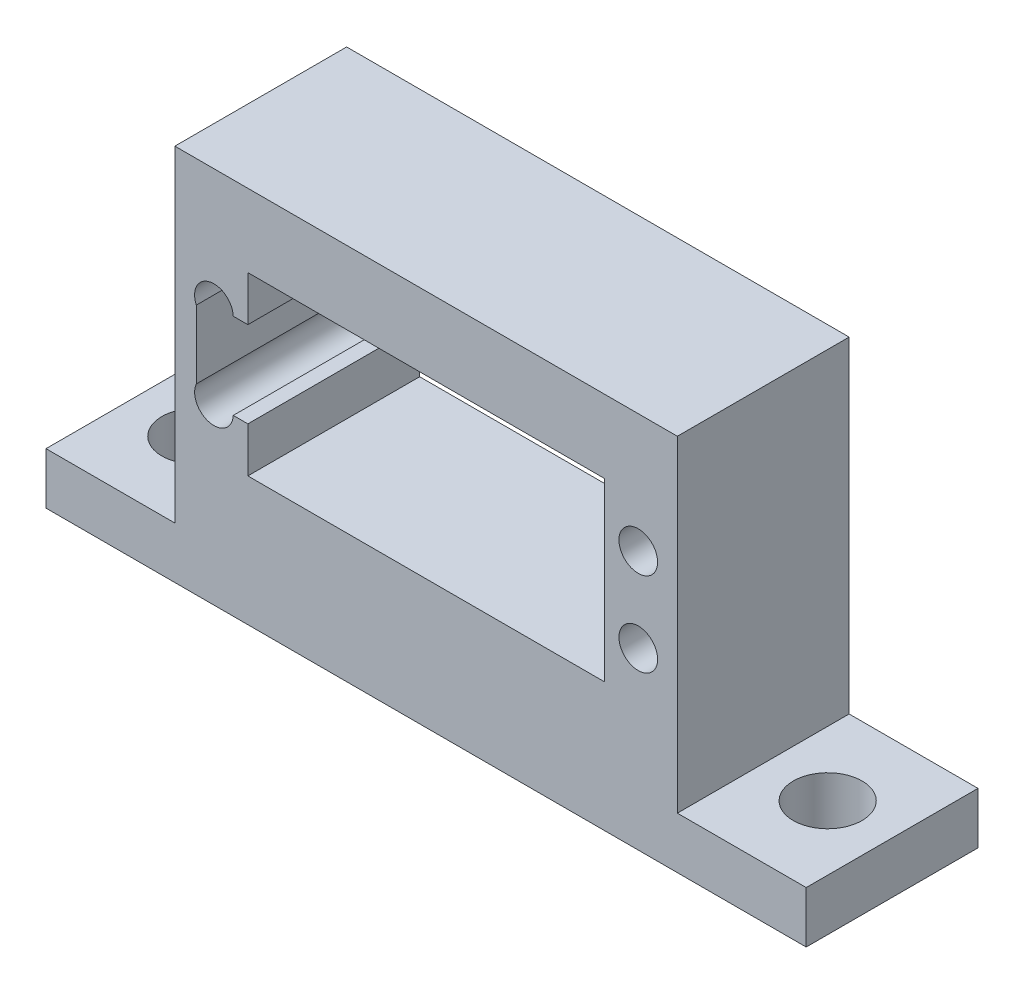
SolidWorks part; units mm, degrees
ref_plane "Front Plane" through (0, 0, 0) normal (0, 0, 1) x (1, 0, 0)
ref_plane "Top Plane" through (0, 0, 0) normal (0, 1, 0) x (1, 0, 0)
ref_plane "Right Plane" through (0, 0, 0) normal (1, 0, 0) x (0, 0, -1)
sketch "Sketch1" plane through (0, 0, 0) normal (0, 0, 1) x (1, 0, 0)
  line L0 (-44.25, 0) -> (44.25, 0)
  line L1 (44.25, 0) -> (44.25, 6)
  line L2 (44.25, 6) -> (29.25, 6)
  line L3 (29.25, 6) -> (29.25, 44)
  line L4 (29.25, 44) -> (-29.25, 44)
  line L5 (0, 0) -> (0, 132.122) construction
  line L6 (-20.75, 35.5) -> (20.75, 35.5)
  line L7 (20.75, 35.5) -> (20.75, 15)
  line L8 (20.75, 15) -> (-20.75, 15)
  line L10 (-29.25, 6) -> (-29.25, 44)
  line L11 (-44.25, 6) -> (-29.25, 6)
  line L12 (-44.25, 0) -> (-44.25, 6)
  line L13 (-20.75, 30.25) -> (-22.4522, 30.25)
  line L14 (-26.75, 29.2226) -> (-26.75, 21.2774)
  line L15 (-22.4522, 20.25) -> (-20.75, 20.25)
  line L16 (-20.75, 35.5) -> (-20.75, 30.25)
  line L18 (-20.75, 20.25) -> (-20.75, 15)
  line L20 (20.75, 25.25) -> (36.6589, 25.25) construction
  circle A0 centre (24.7, 30.15) radius 2.25
  circle A1 centre (24.7, 20.35) radius 2.25
  arc A2 (-26.75, 21.2774) -> (-22.4522, 20.25) centre (-24.7, 20.35) ccw
  arc A3 (-26.75, 29.2226) -> (-22.4522, 30.25) centre (-24.7, 30.15) cw
  point P15 (-26.75, 25.25)
  point P18 (0, 15)
  point P19 (0, 35.5)
  point P20 (0, 44)
  dimension "D11" = 4.5
  dimension "D1" = 41.5
  dimension "D2" = 20.5
  dimension "D3" = 15
  dimension "D4" = 8.5
  dimension "D5" = 15
  dimension "D6" = 8.5
  dimension "D7" = 6
  dimension "D8" = 10
  dimension "D9" = 6
  dimension "D10" = 49.4
  dimension "D12" = 4.9
  dimension "D13" = 5
extrude "Boss-Extrude1" add sketch "Sketch1" along normal blind 20
sketch "Sketch2" plane through (0, 6, 0) normal (0, 1, 0) x (1, 0, 0)
  line L0 (44.25, -10) -> (-44.25, -10) construction
  line L1 (44.25, -20) -> (44.25, 0) construction
  line L2 (-44.25, -20) -> (-44.25, 0) construction
  line L3 (36.75, 0) -> (36.75, -20) construction
  line L4 (44.25, 0) -> (29.25, 0) construction
  line L5 (44.25, -20) -> (29.25, -20) construction
  line L6 (0, 0) -> (0, -20) construction
  line L7 (29.25, 0) -> (-29.25, 0) construction
  line L8 (29.25, -20) -> (-29.25, -20) construction
  circle A0 centre (36.75, -10) radius 4
  circle A1 centre (-36.75, -10) radius 4
  dimension "D1" = 8
extrude "Cut-Extrude1" cut sketch "Sketch2" against normal through all
